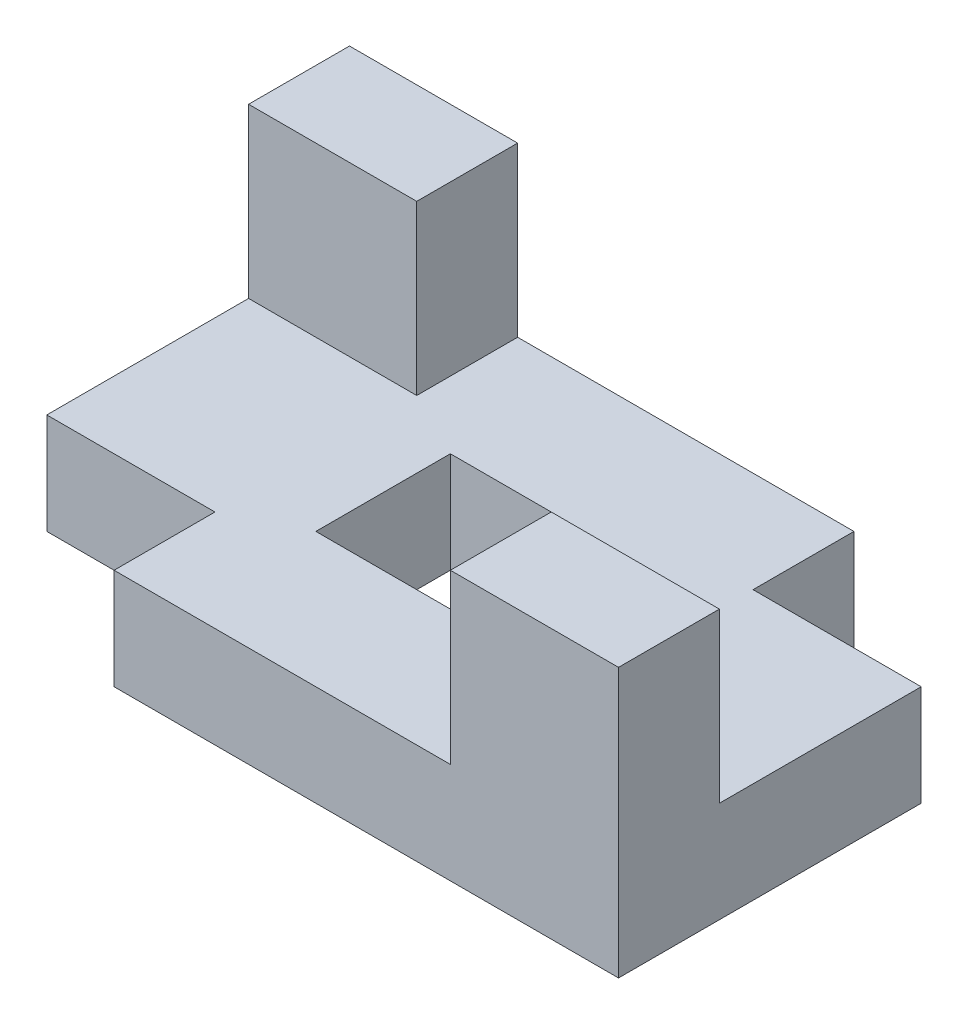
SolidWorks part; units mm, degrees
ref_plane "Front Plane" through (0, 0, 0) normal (0, 0, 1) x (1, 0, 0)
ref_plane "Top Plane" through (0, 0, 0) normal (0, 1, 0) x (1, 0, 0)
ref_plane "Right Plane" through (0, 0, 0) normal (1, 0, 0) x (0, 0, -1)
sketch "Sketch1" plane through (0, 0, 0) normal (0, 1, 0) x (1, 0, 0)
  line L1 (-50, 30) -> (50, 30)
  line L2 (-50, 30) -> (-50, -30)
  line L3 (-50, -30) -> (50, -30)
  line L4 (50, 30) -> (50, -30)
  point P7 (33.0682, -33.6648)
  dimension "D1" = 60
  dimension "D2" = 100
  dimension "D3" = 30
  dimension "D4" = 50
extrude "Boss-Extrude1" add sketch "Sketch1" along normal blind 15 contours L2 L1 L4 L3
sketch "Sketch3" plane through (0, 15, 0) normal (0, 1, 0) x (1, 0, 0)
  line L1 (-50, 30) -> (-25, 30)
  line L2 (-50, 30) -> (-50, 15)
  line L3 (-50, 15) -> (-25, 15)
  line L4 (-25, 30) -> (-25, 15)
  line L5 (50, -30) -> (25, -30)
  line L6 (50, -30) -> (50, -15)
  line L7 (50, -15) -> (25, -15)
  line L8 (25, -30) -> (25, -15)
  point P10 (0, 0)
  dimension "D1" = 15
  dimension "D2" = 25
extrude "Boss-Extrude3" add sketch "Sketch3" along normal blind 25 contours L4 L3 L2 L1
extrude "Boss-Extrude5" add sketch "Sketch3<6>" along normal blind 25 contours L8 L7 L6 L5
sketch "Sketch3<6>" plane through (0, 15, 0) normal (0, 1, 0) x (1, 0, 0) same geometry as "Sketch3"
sketch "Sketch6" plane through (0, 15, 0) normal (0, 1, 0) x (1, 0, 0)
  line L0 (-50, 15) -> (-25, 15) construction
  line L1 (50, 30) -> (25, 30)
  line L2 (50, 30) -> (50, 15)
  line L3 (50, 15) -> (25, 15)
  line L4 (25, 30) -> (25, 15)
  line L5 (-50, -30) -> (-25, -30)
  line L6 (-50, -30) -> (-50, -15)
  line L7 (-50, -15) -> (-25, -15)
  line L8 (-25, -30) -> (-25, -15)
  line L9 (-25, 30) -> (-25, 15) construction
  point P14 (0, 0)
extrude "Cut-Extrude1" cut sketch "Sketch6" against normal through all contours L7 L8 L5 L6
extrude "Cut-Extrude2" cut sketch "Sketch6<3>" against normal through all
sketch "Sketch6<3>" plane through (0, 15, 0) normal (0, 1, 0) x (1, 0, 0) same geometry as "Sketch6"
sketch "Sketch7" plane through (0, 15, 0) normal (0, 1, 0) x (1, 0, 0)
  line L0 (-50, 15) -> (-50, -15) construction
  line L1 (-15, 10) -> (15, 10)
  line L2 (-15, 10) -> (-15, -10)
  line L3 (-15, -10) -> (15, -10)
  line L4 (15, 10) -> (15, -10)
  line L5 (-25, -30) -> (25, -30) construction
  point P8 (0, 0)
  dimension "D1" = 20
  dimension "D2" = 30
  dimension "D3" = 35
  dimension "D4" = 20
extrude "Cut-Extrude3" cut sketch "Sketch7" against normal through all
